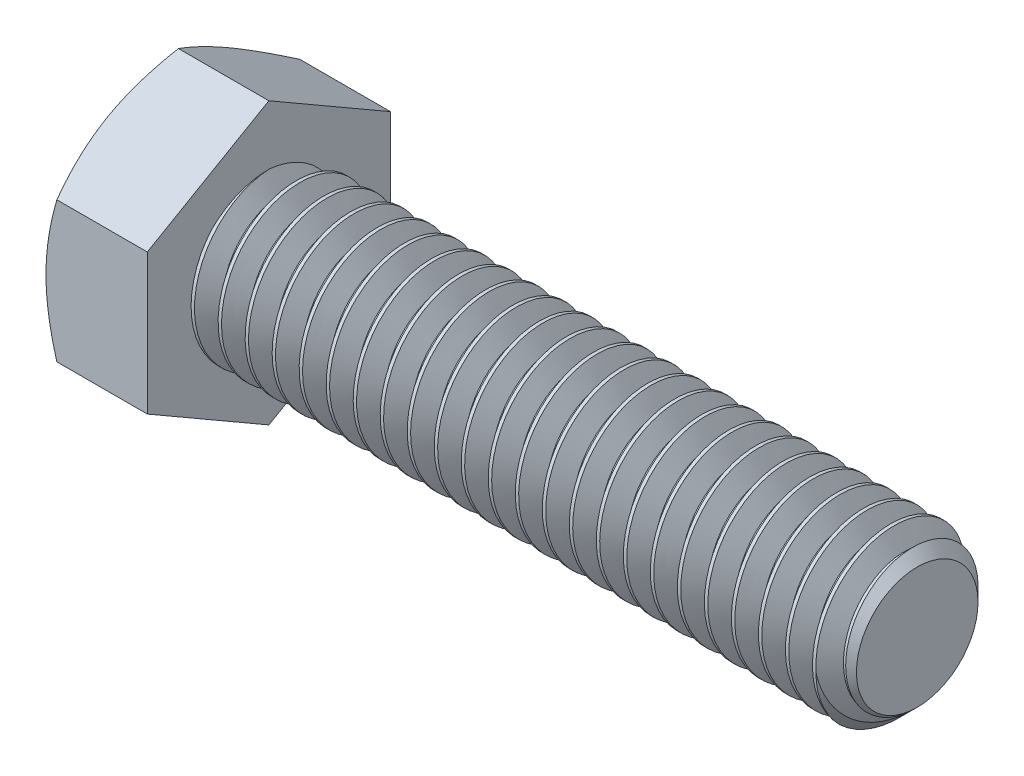
SolidWorks part; units mm, degrees
ref_plane "Front Plane" through (0, 0, 0) normal (0, 0, 1) x (1, 0, 0)
ref_plane "Top Plane" through (0, 0, 0) normal (0, 1, 0) x (1, 0, 0)
ref_plane "Right Plane" through (0, 0, 0) normal (1, 0, 0) x (0, 0, -1)
sketch "Sketch1" plane through (0, 0, 0) normal (0, 0, 1) x (1, 0, 0)
  line L0 (-22.0266, 0) -> (22.0266, 0) construction
  line L1 (22.0266, 4.7625) -> (22.0266, -4.7625) construction
  line L2 (-16.0734, 7.1437) -> (-16.0734, -7.1437) construction
  line L3 (-22.0266, 7.1437) -> (-22.0266, -7.1437) construction
  point P9 (-16.0734, 0)
  point P10 (16.4703, -4.7625)
  dimension "D1" = 5.5562
  dimension "Screw Dia" = 9.525
  dimension "Hex" = 14.2875
  dimension "Head Ht" = 5.9531
  dimension "Screw Lenght" = 38.1
ref_plane "Plane2" through (22.0266, 0, 0) normal (1, 0, 0) x (0, 0, -1)
sketch "Sketch5" plane through (22.0266, 0, 0) normal (1, 0, 0) x (0, 0, -1)
  circle A0 centre (0, 0) radius 4.7625
extrude "Boss-Extrude3" add sketch "Sketch5" against normal up to vertex (38.1 mm away) up to point (-16.0734, 0, 0)
sketch "Sketch9" plane through (22.0266, 0, 0) normal (1, 0, 0) x (0, 0, -1)
  circle A1 centre (0, 0) radius 4.7625
  circle A2 centre (0, 0) radius 4.7625
  dimension "D1" = 0
curve "Helix/Spiral1" pitch 1.5875 height 39.6875 turns 25 parameters "Pitch"=1.5875
chamfer "Chamfer1" distance 1.1906 angle 45 1 edges at (22.0266, 0, -4.7625)
sketch "Sketch10" plane through (0, 0, 0) normal (0, 0, 1) x (1, 0, 0)
  line L0 (22.0266, 4.7625) -> (22.6219, 3.7314)
  line L1 (22.6219, 3.7314) -> (22.8203, 3.7314)
  line L2 (22.8203, 3.7314) -> (23.4156, 4.7625)
  line L3 (22.0266, 4.7625) -> (23.4156, 4.7625)
  line L4 (22.7211, 4.7625) -> (22.7211, 3.7314) construction
  line L5 (22.3242, 4.2469) -> (23.118, 4.2469) construction
  dimension "D1" = 60
  dimension "D2" = 0.1984
  dimension "D3" = 0.7937
sweep "Cut-Sweep1" cut profiles "Sketch10" path "Helix/Spiral1"
sketch "Sketch6" plane through (-16.0734, 0, 0) normal (-1, 0, 0) x (0, 0, 1)
  line L0 (0, 7.1437) -> (0, -7.1437) construction
  line L1 (7.1437, 4.1244) -> (0, 8.2489)
  line L2 (0, 8.2489) -> (-7.1437, 4.1244)
  line L3 (-7.1437, 4.1244) -> (-7.1437, -4.1244)
  line L4 (-7.1437, -4.1244) -> (0, -8.2489)
  line L5 (0, -8.2489) -> (7.1438, -4.1244)
  line L6 (7.1438, -4.1244) -> (7.1437, 4.1244)
  circle A0 centre (0, 0) radius 7.1438 construction
extrude "Boss-Extrude4" add sketch "Sketch6" along normal up to vertex (5.9531 mm away) up to point (-22.0266, -7.1437, 0)
sketch "Sketch7" plane through (-22.0266, 0, 0) normal (-1, 0, 0) x (0, 0, 1)
  circle A0 centre (0, 0) radius 7.1438 construction
  circle A1 centre (0, 0) radius 7.1438
sketch "Sketch8" plane through (-22.0266, 0, 0) normal (-1, 0, 0) x (0, 0, 1)
  circle A0 centre (0, 0) radius 7.1438 construction
  circle A1 centre (0, 0) radius 7.1438
extrude "Cut-Extrude3" cut sketch "Sketch8" against normal through all draft 60 flip side to cut
equation "\"D2@Sketch10\" = \"Pitch@Helix/Spiral1\"*.125"
equation "\"D3@Sketch10\" = \"Pitch@Helix/Spiral1\"*.5"
equation "\"D3@Helix/Spiral1\" = \"Screw Lenght@Sketch1\"+\"Pitch@Helix/Spiral1\""
equation "\"D1@Chamfer1\" = \"Pitch@Helix/Spiral1\"*.75"
equation "\"D1@Sketch1\" = \"Pitch@Helix/Spiral1\"*3.5"
